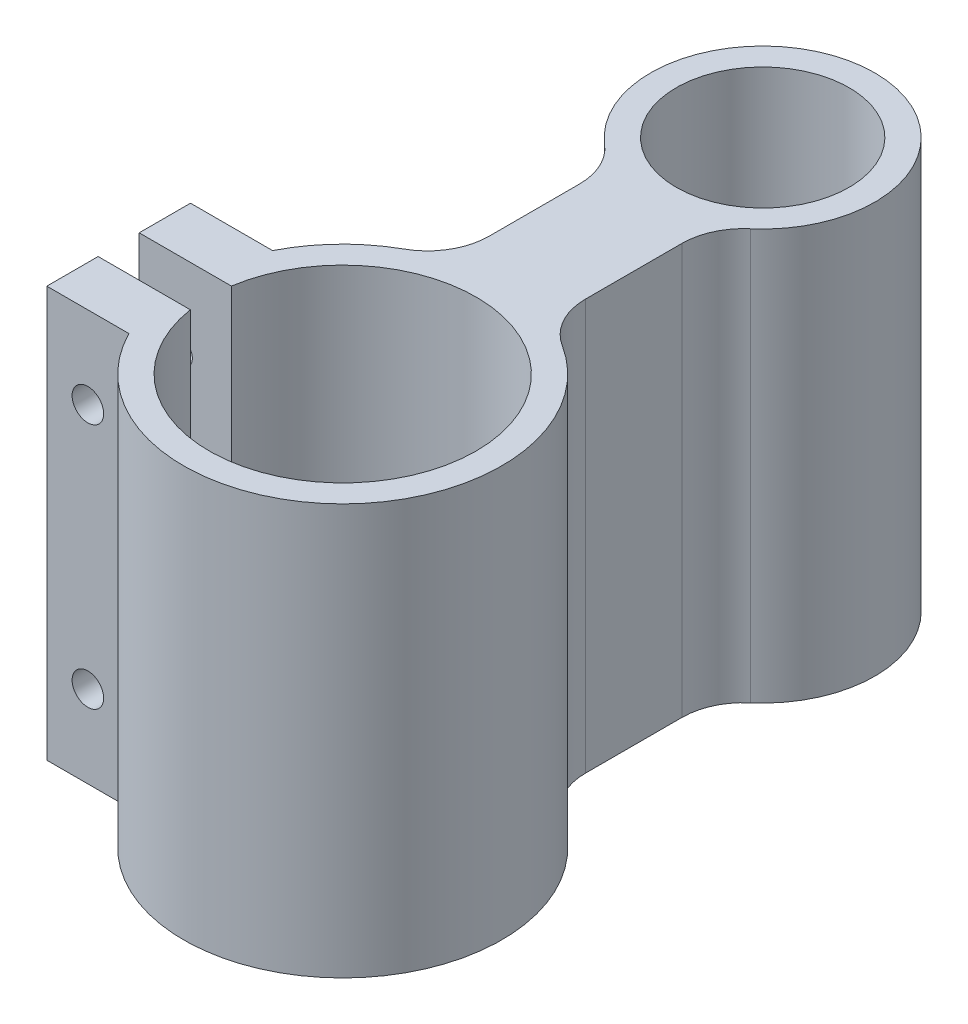
SolidWorks part; units mm, degrees
note: '?' marks a value the reader was unsure of.
material "ABS"
ref_plane "Front" through (0, 0, 0) normal (0, 0, 1) x (1, 0, 0)
ref_plane "Top" through (0, 0, 0) normal (0, 1, 0) x (1, 0, 0)
ref_plane "Right" through (0, 0, 0) normal (1, 0, 0) x (0, 0, -1)
ref_axis "Center Axis" through (0, 0, -88.99) along (0, 0, 1)?
sketch "Sketch1" plane through (0, 0, 0) normal (0, 1, 0) x (1, 0, 0)
  line L1 (-3.7431, -21.0686) -> (-31.0885, -21.0686)
  line L2 (-3.7431, -21.0686) -> (-3.7431, -15.9886)
  line L3 (-3.7431, -15.9886) -> (-31.0885, -15.9886)
  line L4 (-31.0885, -21.0686) -> (-31.0885, -15.9886)
  line L5 (-3.7431, -21.0686) -> (-31.0885, -15.9886) construction
  line L6 (-3.7431, -15.9886) -> (-31.0885, -21.0686) construction
  line L7 (-17.4158, -15.9886) -> (-27.5758, -15.9886)
  line L8 (-17.4158, -15.9886) -> (-17.4158, -9.6386)
  line L9 (-17.4158, -9.6386) -> (-27.5758, -9.6386)
  line L10 (-27.5758, -15.9886) -> (-27.5758, -9.6386)
  line L11 (-17.4158, -21.0686) -> (-27.5758, -21.0686)
  line L12 (-17.4158, -21.0686) -> (-17.4158, -27.4186)
  line L13 (-17.4158, -27.4186) -> (-27.5758, -27.4186)
  line L14 (-27.5758, -21.0686) -> (-27.5758, -27.4186)
  line L15 (-5.5628, 20.4671) -> (7.1372, 20.4671)
  line L16 (-5.5628, 20.4671) -> (-5.5628, -0.1263)
  line L17 (-5.5628, -0.1263) -> (7.1372, -0.1263)
  line L18 (7.1372, 20.4671) -> (7.1372, -0.1263)
  circle A0 centre (0.7872, 32.7963) radius 10.6934
  circle A1 centre (0.1474, -18.5286) radius 16.51
  circle A2 centre (0.7872, 32.7963) radius 13.8684
  circle A3 centre (0.1474, -18.5286) radius 19.685
  point P4 (0.7872, 22.1029)
  point P9 (0.1474, -2.0186)
  point P11 (-17.4158, -18.5286)
  dimension "D1" = 21.3868
  dimension "D2" = 33.02
  dimension "D3" = 24.13
  dimension "D5" = 5.08
  dimension "D6" = 6.35
  dimension "D7" = 10.16
  dimension "D8" = 12.7
  dimension "D4" = 3.175
extrude "Boss-Extrude1" add sketch "Sketch1" along normal blind 50.8 contours A3 A2 A0 | A2 A3 | L8 L7 L10 L9 | L12 L11 L14 L13 | L16 L15 L18 L17
fillet "Fillet1" radius 7.62 4 edges at (7.1372, 25.4, 0.1263) (7.1372, 25.4, -20.4671) (-5.5628, 25.4, -0.31) (-5.5628, 25.4, -20.4671)
sketch "Sketch2" plane through (0, 0, 21.0686) normal (0, 0, -1) x (-1, 0, 0)
  line L1 (27.5758, 25.4) -> (17.4158, 25.4) construction
  line L2 (27.5758, 50.8) -> (27.5758, 0) construction
  line L3 (17.4158, 50.8) -> (17.4158, 0) construction
  line L4 (17.4158, 50.8) -> (17.4158, 0) construction
  circle A0 centre (22.4958, 40.64) radius 1.95
  circle A1 centre (22.4958, 10.16) radius 1.95
  point P3 (22.4958, 50.8)
  dimension "D1" = 3.9
  dimension "D2" = 15.24
  dimension "D3" = 5.08
extrude "Cut-Extrude1" cut sketch "Sketch2" against normal through all
sketch "Sketch3" plane through (0, 0, 9.6386) normal (0, 0, -1) x (-1, 0, 0)
  circle A0 centre (22.4958, 40.64) radius 1.5
  circle A1 centre (22.4958, 10.16) radius 1.95
  circle A2 centre (22.4958, 10.16) radius 1.95
  circle A3 centre (22.4958, 40.64) radius 1.95
  circle A4 centre (22.4958, 40.64) radius 1.95
  circle A5 centre (22.4958, 10.16) radius 1.5
  dimension "D3" = 3
  dimension "D1" = 0
  dimension "D2" = 0
extrude "Cut-Extrude3" cut sketch "Sketch3" against normal up to next contours A5 | A0
